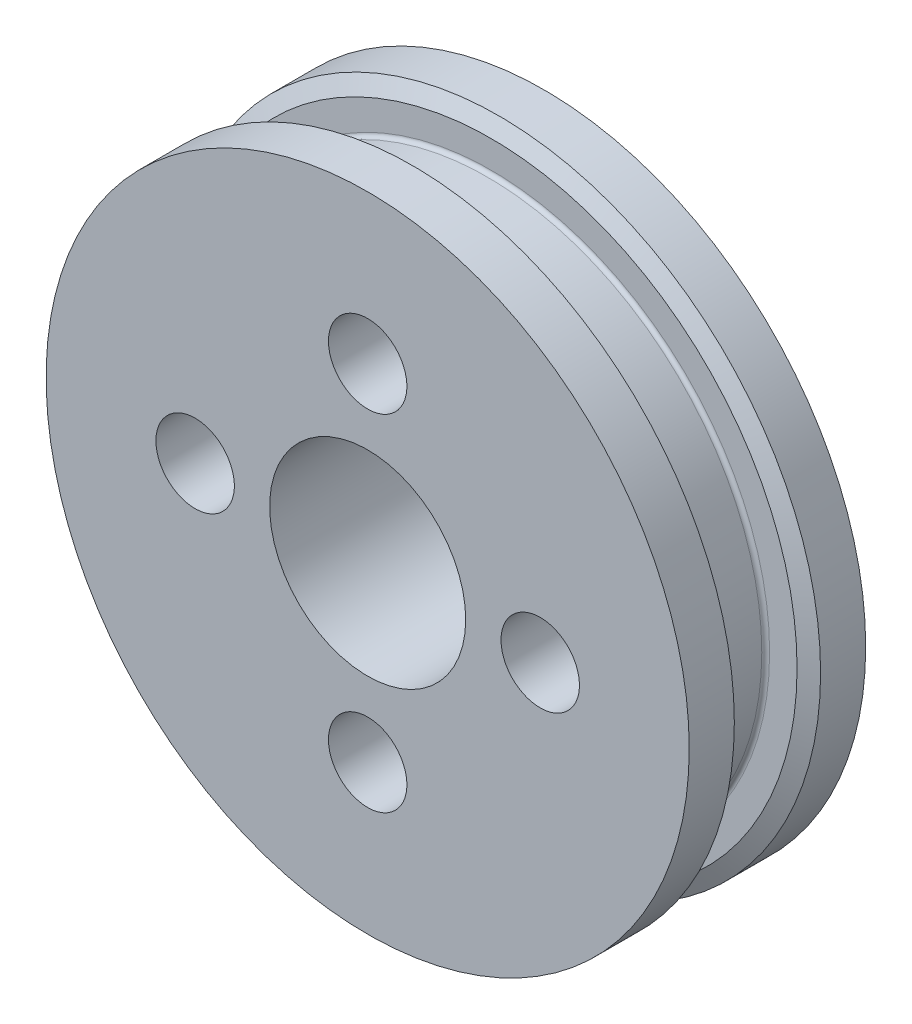
SolidWorks part; units mm, degrees
ref_plane "Front Plane" through (0, 0, 0) normal (0, 0, 1) x (1, 0, 0)
ref_plane "Top Plane" through (0, 0, 0) normal (0, 1, 0) x (1, 0, 0)
ref_plane "Right Plane" through (0, 0, 0) normal (1, 0, 0) x (0, 0, -1)
sketch "Sketch2" plane through (0, 0, 0) normal (1, 0, 0) x (0, 0, -1)
  line L0 (0, 6.35) -> (0, 20.828)
  line L1 (0, 20.828) -> (2.921, 20.828)
  line L2 (3.429, 19.812) -> (3.429, 17.78)
  line L3 (3.429, 17.78) -> (8.001, 17.78)
  line L4 (8.001, 17.78) -> (8.001, 19.812)
  line L5 (8.509, 20.828) -> (11.43, 20.828)
  line L6 (11.43, 20.828) -> (11.43, 6.35)
  line L8 (0, 6.35) -> (11.43, 6.35)
  line L9 (0, 6.35) -> (0, 0) construction
  line L10 (0, 0) -> (10.7816, 0) construction
  line L11 (8.001, 19.812) -> (8.509, 20.828)
  line L12 (2.921, 20.828) -> (3.429, 19.812)
  point P4 (3.429, 20.828)
  point P7 (8.001, 20.828)
  dimension "D1" = 17.78
  dimension "D2" = 11.43
  dimension "D3" = 3.048
  dimension "D4" = 6.35
  dimension "D5" = 4.572
  dimension "D6" = 1.016
  dimension "D7" = 0.508
  dimension "D8" = 0.508
  dimension "D9" = 1.016
revolve "Revolve1" add sketch "Sketch2" angle 360 about L10
sketch "Sketch3" plane through (0, 0, -11.43) normal (0, 0, -1) x (-1, 0, 0)
  line L1 (-8.255, -8.255) -> (8.255, -8.255)
  line L2 (-8.255, -8.255) -> (-8.255, 8.255)
  line L3 (-8.255, 8.255) -> (8.255, 8.255)
  line L4 (8.255, -8.255) -> (8.255, 8.255)
  circle A0 centre (0, 0) radius 6.35 construction
  circle A1 centre (0, 0) radius 6.35
  point P4 (8.255, 0)
  point P6 (0, 8.255)
  dimension "D1" = 16.51
extrude "Boss-Extrude1" add sketch "Sketch3" along normal blind 3.175
ref_plane "Plane1" through (0, 0, -5.715) normal (0, 0, -1) x (-1, 0, 0)
sketch "Sketch4" plane through (0, 0, -11.43) normal (0, 0, -1) x (-1, 0, 0)
  line L0 (0, 11.176) -> (0, 0) construction
  line L1 (0, 0) -> (0, -11.176) construction
  line L2 (-11.176, 0) -> (0, 0) construction
  line L3 (0, 0) -> (11.176, 0) construction
  circle A0 centre (0, 11.176) radius 2.54
  circle A1 centre (11.176, 0) radius 2.54
  circle A2 centre (0, -11.176) radius 2.54
  circle A3 centre (-11.176, 0) radius 2.54
  dimension "D1" = 5.08
  dimension "D2" = 11.176
extrude "Cut-Extrude1" cut sketch "Sketch4" against normal through all both and the other way through all
fillet "Fillet1" radius 0.254 2 edges at (17.78, 0, -8.001) (17.78, 0, -3.429)
